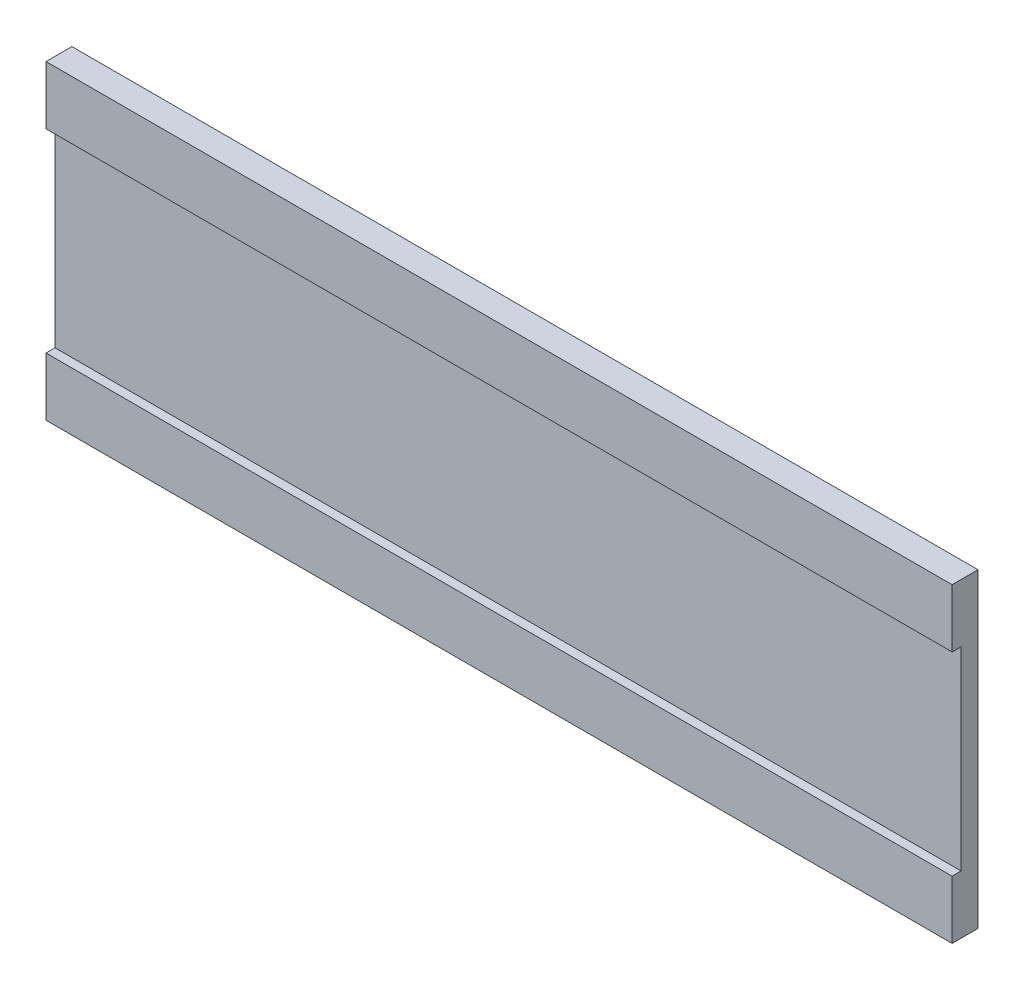
SolidWorks part; units mm, degrees
ref_plane "Plan de face" through (0, 0, 0) normal (0, 0, 1) x (1, 0, 0)
ref_plane "Plan de dessus" through (0, 0, 0) normal (0, 1, 0) x (1, 0, 0)
ref_plane "Plan de droite" through (0, 0, 0) normal (1, 0, 0) x (0, 0, -1)
sketch "Esquisse1" plane through (0, 0, 0) normal (0, 0, 1) x (1, 0, 0)
  line L1 (-33.559, 25.9394) -> (106.441, 25.9394)
  line L2 (-33.559, 25.9394) -> (-33.559, -22.0606)
  line L3 (-33.559, -22.0606) -> (106.441, -22.0606)
  line L4 (106.441, 25.9394) -> (106.441, -22.0606)
  dimension "D1" = 48
  dimension "D2" = 140
extrude "Boss.-Extru.1" add sketch "Esquisse1" along normal blind 4
sketch "Esquisse2" plane through (-33.559, 0, 0) normal (-1, 0, 0) x (0, 0, 1)
  line L0 (4, 25.9394) -> (4, -22.0606) construction
  line L1 (4, 16.9394) -> (2.6099, 16.9394)
  line L2 (4, 16.9394) -> (4, -13.0606)
  line L3 (4, -13.0606) -> (2.6099, -13.0606)
  line L4 (2.6099, 16.9394) -> (2.6099, -13.0606)
  line L5 (4, 25.9394) -> (0, 25.9394) construction
  line L6 (4, -22.0606) -> (0, -22.0606) construction
  dimension "D1" = 9
  dimension "D2" = 9
extrude "Enlèv. mat.-Extru.1" cut sketch "Esquisse2" against normal through all
